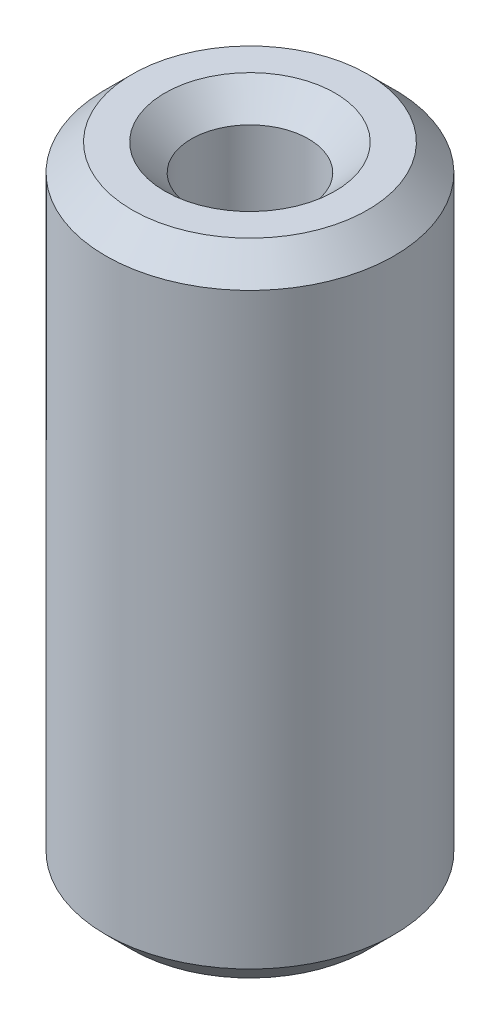
SolidWorks part; units mm, degrees
ref_plane "Front Plane" through (0, 0, 0) normal (0, 0, 1) x (1, 0, 0)
ref_plane "Top Plane" through (0, 0, 0) normal (0, 1, 0) x (1, 0, 0)
ref_plane "Right Plane" through (0, 0, 0) normal (1, 0, 0) x (0, 0, -1)
sketch "Sketch1" plane through (0, 0, 0) normal (0, 1, 0) x (1, 0, 0)
  circle A0 centre (0, 0) radius 20
  dimension "SLEEVE_OD" = 40
extrude "Boss-Extrude1" add sketch "Sketch1" along normal blind 88.8599
sketch "Sketch2" plane through (0, 0, 0) normal (0, 1, 0) x (1, 0, 0)
  circle A0 centre (0, 0) radius 8.1243
  dimension "BORE_D" = 16.2486
extrude "Cut-Extrude1" cut sketch "Sketch2" along normal through all
chamfer "Chamfer1" distance 3.6758 angle 45 4 edges at (0, 88.8599, 8.1243) (0, 0, 8.1243) (0, 0, 20) (0, 88.8599, 20)
